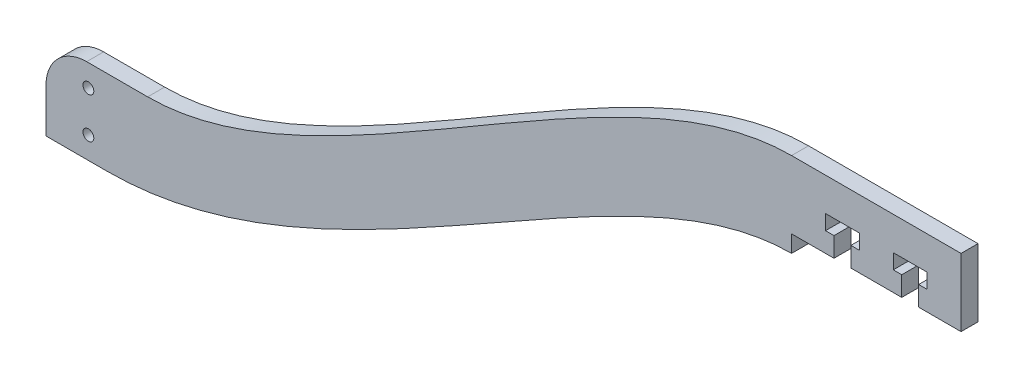
SolidWorks part; units mm, degrees
ref_plane "Front Plane" through (0, 0, 0) normal (0, 0, 1) x (1, 0, 0)
ref_plane "Top Plane" through (0, 0, 0) normal (0, 1, 0) x (1, 0, 0)
ref_plane "Right Plane" through (0, 0, 0) normal (1, 0, 0) x (0, 0, -1)
sketch "Sketch1" plane through (0, 0, 0) normal (0, 0, 1) x (1, 0, 0)
  line L1 (-139.7, -42.545) -> (-139.7, -50.8)
  line L2 (-71.502, -34.925) -> (-125.3505, -34.925) construction
  line L3 (0, 0) -> (0, 3.175)
  line L4 (0, 3.175) -> (7.9375, 3.175)
  line L5 (31.75, 3.175) -> (31.75, 15.875)
  line L6 (31.75, 15.875) -> (0, 15.875)
  line L7 (0, -1000) -> (0, 49000) construction
  line L8 (9.525, -988.6477) -> (9.525, 49011.3523) construction
  line L9 (22.225, -989.9681) -> (22.225, 49010.0319) construction
  line L10 (7.9375, 3.175) -> (7.9375, 6.858)
  line L11 (7.9375, 6.858) -> (6.35, 6.858)
  line L12 (6.35, 6.858) -> (6.35, 9.652)
  line L13 (6.35, 9.652) -> (12.7, 9.652)
  line L14 (12.7, 9.652) -> (12.7, 6.858)
  line L15 (12.7, 6.858) -> (11.1125, 6.858)
  line L16 (11.1125, 6.858) -> (11.1125, 3.175)
  line L17 (11.1125, 3.175) -> (20.6375, 3.175)
  line L18 (20.6375, 3.175) -> (20.6375, 6.858)
  line L19 (20.6375, 6.858) -> (19.05, 6.858)
  line L20 (19.05, 6.858) -> (19.05, 9.652)
  line L21 (19.05, 9.652) -> (25.4, 9.652)
  line L22 (25.4, 9.652) -> (25.4, 6.858)
  line L23 (25.4, 6.858) -> (23.8125, 6.858)
  line L24 (23.8125, 6.858) -> (23.8125, 3.175)
  line L25 (23.8125, 3.175) -> (31.75, 3.175)
  line L26 (-131.7625, -1027.5749) -> (-131.7625, 48972.4251) construction
  line L27 (-128.27, -50.8) -> (-139.7, -50.8)
  line L28 (-120.65, -34.925) -> (-132.08, -34.925)
  line L29 (-127, -264.16) -> (-120.65, -34.925) construction
  line L30 (-71.502, -50.8) -> (-125.3505, -50.8) construction
  line L32 (26.7231, 15.875) -> (-26.7231, 15.875) construction
  line L33 (26.3977, 0) -> (-26.3989, 0) construction
  circle A0 centre (-131.7625, -39.0525) radius 1.016
  circle A1 centre (-131.7625, -46.6725) radius 1.016
  arc A2 (-132.08, -34.925) -> (-139.7, -42.545) centre (-132.08, -42.545) ccw
  spline S0 degree 3 poles (-120.65, -34.925) (-86.9947, -34.925) (-33.4039, 15.875) (0, 15.875) knots 0 0 0 0 1 1 1 1
  spline S1 degree 3 poles (-128.27, -50.8) (-84.7243, -50.8) (-32.9979, 0) (0, 0) knots 0 0 0 0 1 1 1 1
  point P23 (9.525, 9.652)
  point P31 (22.225, 9.652)
  point P48 (-139.7, -34.925)
  dimension "D14" = 2.032
  dimension "D17" = 7.62
  dimension "D1" = 3.175
  dimension "D2" = 15.875
  dimension "D3" = 15.875
  dimension "D4" = 139.7
  dimension "D5" = 31.75
  dimension "D6" = 9.525
  dimension "D7" = 12.7
  dimension "D8" = 6.35
  dimension "D9" = 2.794
  dimension "D10" = 6.477
  dimension "D11" = 3.175
  dimension "D12" = 50.8
  dimension "D13" = 7.9375
  dimension "D15" = 4.1275
  dimension "D16" = 7.62
extrude "Boss-Extrude1" add sketch "Sketch1" along normal blind 3.175
